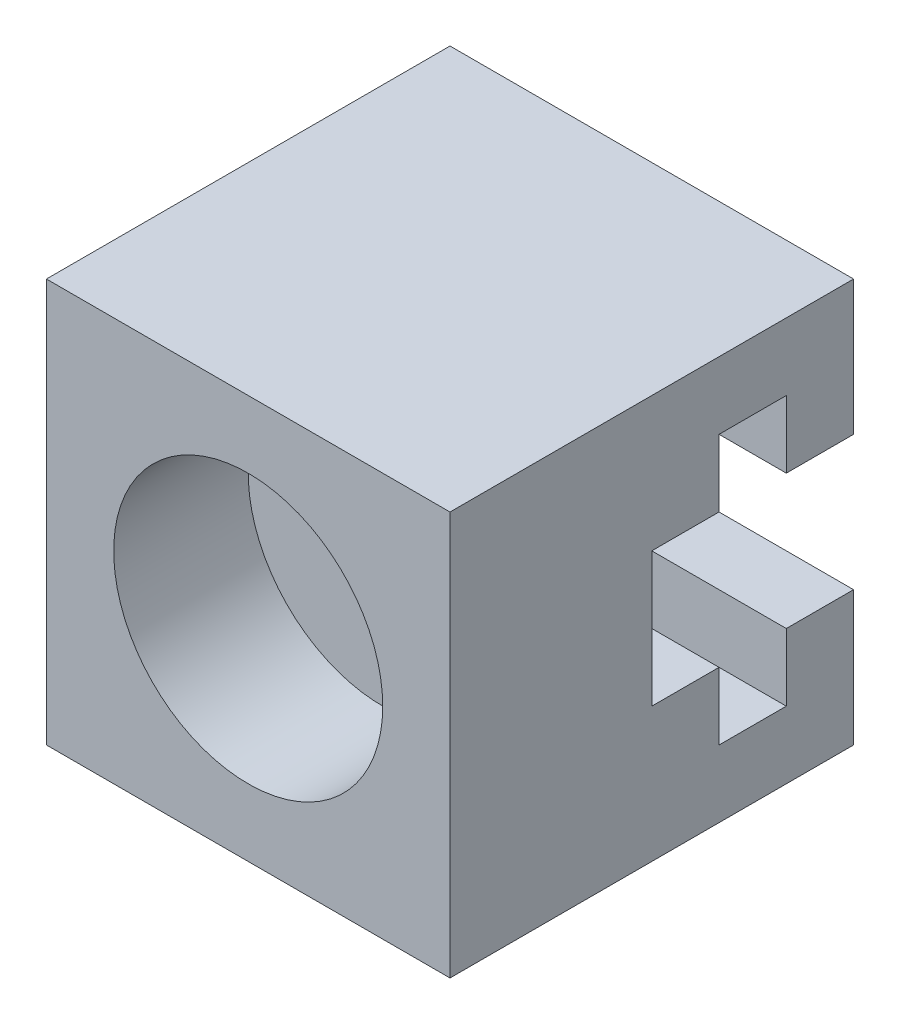
SolidWorks part; units mm, degrees
ref_plane "Front Plane" through (0, 0, 0) normal (0, 0, 1) x (1, 0, 0)
ref_plane "Top Plane" through (0, 0, 0) normal (0, 1, 0) x (1, 0, 0)
ref_plane "Right Plane" through (0, 0, 0) normal (1, 0, 0) x (0, 0, -1)
other "Center of Mass"
sketch "Sketch2" plane through (0, 0, 0) normal (1, 0, 0) x (0, 0, -1)
  line L0 (75, 25) -> (50, 25)
  line L1 (-75, 75) -> (75, 75)
  line L2 (-75, 75) -> (-75, -75)
  line L3 (-75, -75) -> (75, -75)
  line L4 (75, 75) -> (75, 25)
  line L5 (-75, 75) -> (75, -75) construction
  line L6 (-75, -75) -> (75, 75) construction
  line L7 (50, 25) -> (50, 50)
  line L8 (50, 50) -> (25, 50)
  line L9 (25, 50) -> (25, 25)
  line L10 (25, 25) -> (0, 25)
  line L11 (0, 25) -> (0, -25)
  line L12 (0, -25) -> (25, -25)
  line L13 (25, -25) -> (25, -50)
  line L14 (25, -50) -> (50, -50)
  line L15 (50, -50) -> (50, -25)
  line L16 (50, -25) -> (75, -25)
  line L18 (75, -25) -> (75, -75)
  point P0 (0, 0)
  dimension "D1" = 150
  dimension "D2" = 150
  dimension "D3" = 25
  dimension "D4" = 25
  dimension "D5" = 75
  dimension "D6" = 25
  dimension "D7" = 25
  dimension "D8" = 50
  dimension "D9" = 50
  dimension "D10" = 25
  dimension "D11" = 50
  dimension "D12" = 50
  dimension "D13" = 25
extrude "Boss-Extrude1" add sketch "Sketch2" against normal blind 75 and the other way blind 75
sketch "Sketch4" plane through (0, 0, 75) normal (0, 0, 1) x (1, 0, 0)
  circle A0 centre (0, 0) radius 50
  dimension "D1" = 100
extrude "Cut-Extrude1" cut sketch "Sketch4" against normal blind 50
